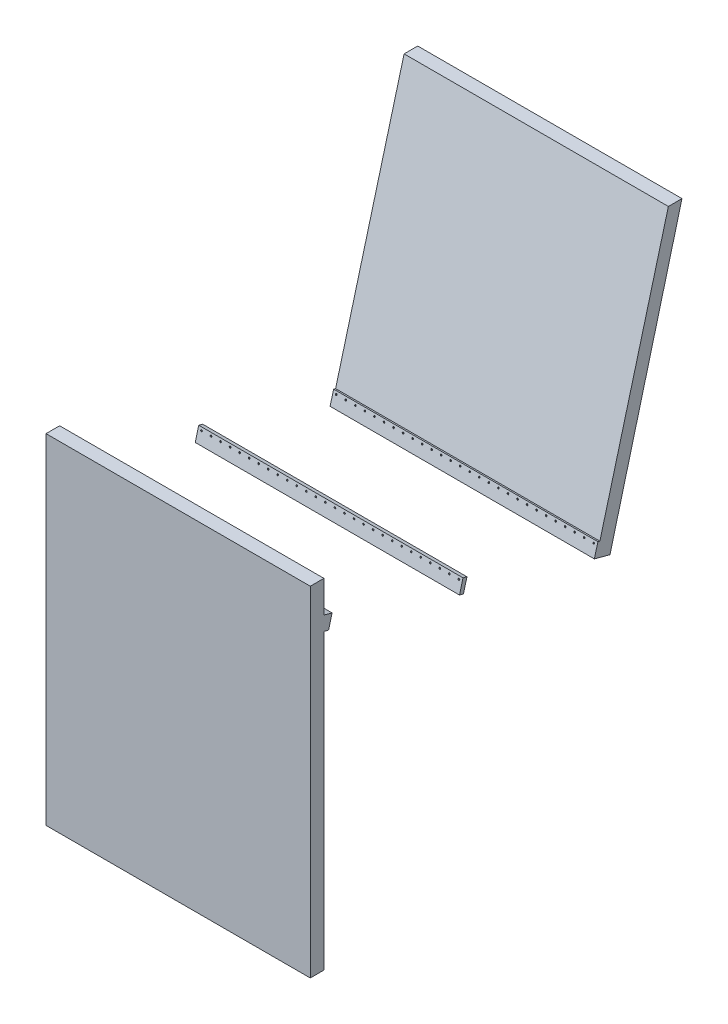
SolidWorks part; units mm, degrees
note: The reader was unsure of these and kept them because the rebuilt part matched: shared geometry of "Sketch1<3>", "Sketch1<5>", "Sketch1<6>".
ref_plane "Front Plane" through (0, 0, 0) normal (0, 0, 1) x (1, 0, 0)
ref_plane "Top Plane" through (0, 0, 0) normal (0, 1, 0) x (1, 0, 0)
ref_plane "Right Plane" through (0, 0, 0) normal (1, 0, 0) x (0, 0, -1)
sketch "Sketch1" plane through (0, 0, 0) normal (0, 1, 0) x (1, 0, 0)
  line L0 (970, -1000) -> (-970, -1000)
  line L1 (-970, -1000) -> (-970, -1100)
  line L2 (-970, -1100) -> (970, -1100)
  line L3 (970, -1100) -> (970, -1000)
  line L4 (-970, 1000) -> (970, 1000)
  line L5 (970, 1000) -> (970, 1100)
  line L6 (970, 1100) -> (-970, 1100)
  line L7 (-970, 1100) -> (-970, 1000)
  point P2 (0, -1000)
  dimension "D1" = 1940
  dimension "D2" = 100
  dimension "D3" = 1000
  dimension "D4" = 100
  dimension "D5" = 1000
  dimension "D6" = 1940
extrude "Boss-Extrude1" add sketch "Sketch1" along normal blind 2000
sketch "Sketch2" plane through (0, 0, 0) normal (1, 0, 0) x (0, 0, -1)
  line L0 (1100, 0) -> (1100, 1200) construction
  line L4 (1100, 2000) -> (1100, 0) construction
  line L7 (1100, 1200) -> (-1100, 1789.4882)
  line L8 (-1100, 2000) -> (-1100, 0) construction
  line L9 (1100, 1200) -> (132.8962, 1200) construction
  line L10 (-1100, 1789.4882) -> (-1100, 2789.4882)
  line L11 (-1100, 2789.4882) -> (1100, 2789.4882)
  line L12 (1100, 2789.4882) -> (1100, 1200)
  dimension "D1" = 1200
  dimension "D2" = 15
  dimension "D3" = 1000
extrude "Cut-Extrude1" cut sketch "Sketch2" against normal through all both and the other way through all
ref_plane "Plane1" through (0, 3200, 0) normal (0, 1, 0) x (1, 0, 0)
sketch "Sketch3" plane through (0, 1394.6152, -373.686) normal (0, 0.9659, -0.2588) x (1, 0, 0)
  line L0 (-970, 648.4079) -> (970, 648.4079)
  line L1 (970, 648.4079) -> (970, 751.9356)
  line L2 (970, 751.9356) -> (-970, 751.9356)
  line L3 (-970, 751.9356) -> (-970, 648.4079)
sketch "Sketch5" plane through (0, 0, 0) normal (1, 0, 0) x (0, 0, -1)
  line L0 (1000, 1226.7949) -> (1000, 2391.2042) construction
  line L1 (1000, 1226.7949) -> (1528.7187, 3200) construction
  line L2 (1067, 3200) -> (-1067, 3200) construction
  dimension "D1" = 15
sketch "Sketch6" plane through (0, 3200, 0) normal (0, 1, 0) x (1, 0, 0)
  line L0 (-970, 1528.7187) -> (970, 1528.7187)
  line L2 (-970, 1100) -> (-970, 1000) construction
  line L4 (0, 1000) -> (0, 1528.7187) construction
  line L5 (-970, 1528.7187) -> (-970, 1628.7187)
  line L6 (-970, 1628.7187) -> (970, 1628.7187)
  line L7 (970, 1628.7187) -> (970, 1528.7187)
  point P3 (0, 1528.7187)
  dimension "D1" = 1940
  dimension "D2" = 100
loft "Loft2" add profiles "Sketch6" section face at (0, 1213.3975, -1050) section "Sketch6"
sketch "Sketch4" plane through (0, 0, 0) normal (1, 0, 0) x (0, 0, -1)
  line L2 (1100, 1200) -> (-1100, 1789.4882)
  line L10 (1100, 1200) -> (1125.5581, 1296.6793)
  line L12 (1125.5581, 1296.6793) -> (-1100, 1893.0158)
  line L13 (-1100, 1893.0158) -> (-1100, 1789.4882)
  line L14 (1100, 1200) -> (1628.7187, 3200) construction
  dimension "D1" = 100
extrude "Boss-Extrude3" add sketch "Sketch4" along normal up to vertex (970 mm away) and the other way up to vertex (970 mm away) up to point (970, 1762.6933, 1000) other way up to point (-970, 1762.6933, 1000)
extrude "Boss-Extrude4" add sketch "Sketch1<3>" along normal blind 2100 contours L0 L1 L2 L3
sketch "Sketch1<3>" plane through (0, 0, 0) normal (0, 1, 0) x (1, 0, 0) same geometry as "Sketch1"
extrude "Cut-Extrude2" cut sketch "Sketch1<5>" along normal up to surface (1226.7949 mm away) contours L6 L7 L4 L5
sketch "Sketch1<5>" plane through (0, 0, 0) normal (0, 1, 0) x (1, 0, 0) same geometry as "Sketch1"
sketch "Sketch7" plane through (0, 1491.2078, -399.5679) normal (0, 0.9659, -0.2588) x (1, 0, 0)
  line L0 (-970, 633.4079) -> (970, 633.4079)
  line L1 (-970, 648.4079) -> (-970, -1448.9393) construction
  line L2 (970, 648.4079) -> (970, -1448.9393) construction
  line L3 (-970, -361.5921) -> (970, -361.5921)
  line L4 (-970, -391.5921) -> (970, -391.5921)
  line L5 (-970, -1386.5921) -> (970, -1386.5921)
  line L6 (-970, 648.4079) -> (970, 648.4079) construction
  line L7 (970, 633.4079) -> (970, -1386.5921)
  line L8 (-970, 633.4079) -> (-970, -1386.5921)
  line M6 (970, -1448.9393) -> (970, 648.4079)
  line M8 (-970, 648.4079) -> (-970, -1448.9393)
  dimension "D1" = 15
  dimension "D2" = 995
  dimension "D3" = 30
  dimension "D4" = 995
extrude "Cut-Extrude3" cut sketch "Sketch7" against normal up to next contours L3 L0 M8 M6 | L5 L4 M8 M6
sketch "Sketch8" plane through (0, -163.938, -611.8251) normal (0, 0.2588, 0.9659) x (1, 0, 0)
  line L0 (-970, 1493.8119) -> (970, 1493.8119) construction
  line L7 (-970, 1443.8119) -> (-970, 1543.8119) construction
  line L8 (970, 1443.8119) -> (970, 1543.8119) construction
  line L11 (0, 1493.8119) -> (0, 1523.8119) construction
  line L167 (-970, 1523.8119) -> (970, 1523.8119) construction
  line L168 (35, 1543.8119) -> (35, 1443.8119) construction
  line L169 (-970, 1543.8119) -> (970, 1543.8119) construction
  line L170 (970, 1443.8119) -> (-970, 1443.8119) construction
  line L171 (-35, 1543.8119) -> (-35, 1443.8119) construction
  line L172 (-108.2079, 1518.2557) -> (-101.7921, 1518.2557)
  line L173 (-28.5842, 1523.8119) -> (-31.7921, 1529.3682)
  line L174 (-31.7921, 1529.3682) -> (-38.2079, 1529.3682)
  line L175 (-38.2079, 1529.3682) -> (-41.4158, 1523.8119)
  line L176 (-41.4158, 1523.8119) -> (-38.2079, 1518.2557)
  line L177 (-38.2079, 1518.2557) -> (-31.7921, 1518.2557)
  line L178 (-31.7921, 1518.2557) -> (-28.5842, 1523.8119)
  line L179 (-101.7921, 1518.2557) -> (-98.5842, 1523.8119)
  line L180 (-98.5842, 1523.8119) -> (-101.7921, 1529.3682)
  line L181 (-101.7921, 1529.3682) -> (-108.2079, 1529.3682)
  line L182 (-108.2079, 1529.3682) -> (-111.4158, 1523.8119)
  line L183 (-111.4158, 1523.8119) -> (-108.2079, 1518.2557)
  line L184 (-178.2079, 1518.2557) -> (-171.7921, 1518.2557)
  line L185 (-171.7921, 1518.2557) -> (-168.5842, 1523.8119)
  line L186 (-168.5842, 1523.8119) -> (-171.7921, 1529.3682)
  line L187 (-171.7921, 1529.3682) -> (-178.2079, 1529.3682)
  line L188 (-178.2079, 1529.3682) -> (-181.4158, 1523.8119)
  line L189 (-181.4158, 1523.8119) -> (-178.2079, 1518.2557)
  line L190 (-248.2079, 1518.2557) -> (-241.7921, 1518.2557)
  line L191 (-241.7921, 1518.2557) -> (-238.5842, 1523.8119)
  line L192 (-238.5842, 1523.8119) -> (-241.7921, 1529.3682)
  line L193 (-241.7921, 1529.3682) -> (-248.2079, 1529.3682)
  line L194 (-248.2079, 1529.3682) -> (-251.4158, 1523.8119)
  line L195 (-251.4158, 1523.8119) -> (-248.2079, 1518.2557)
  line L196 (-318.2079, 1518.2557) -> (-311.7921, 1518.2557)
  line L197 (-311.7921, 1518.2557) -> (-308.5842, 1523.8119)
  line L198 (-308.5842, 1523.8119) -> (-311.7921, 1529.3682)
  line L199 (-311.7921, 1529.3682) -> (-318.2079, 1529.3682)
  line L200 (-318.2079, 1529.3682) -> (-321.4158, 1523.8119)
  line L201 (-321.4158, 1523.8119) -> (-318.2079, 1518.2557)
  line L202 (-388.2079, 1518.2557) -> (-381.7921, 1518.2557)
  line L203 (-381.7921, 1518.2557) -> (-378.5842, 1523.8119)
  line L204 (-378.5842, 1523.8119) -> (-381.7921, 1529.3682)
  line L205 (-381.7921, 1529.3682) -> (-388.2079, 1529.3682)
  line L206 (-388.2079, 1529.3682) -> (-391.4158, 1523.8119)
  line L207 (-391.4158, 1523.8119) -> (-388.2079, 1518.2557)
  line L208 (-458.2079, 1518.2557) -> (-451.7921, 1518.2557)
  line L209 (-451.7921, 1518.2557) -> (-448.5842, 1523.8119)
  line L210 (-448.5842, 1523.8119) -> (-451.7921, 1529.3682)
  line L211 (-451.7921, 1529.3682) -> (-458.2079, 1529.3682)
  line L212 (-458.2079, 1529.3682) -> (-461.4158, 1523.8119)
  line L213 (-461.4158, 1523.8119) -> (-458.2079, 1518.2557)
  line L214 (-528.2079, 1518.2557) -> (-521.7921, 1518.2557)
  line L215 (-521.7921, 1518.2557) -> (-518.5842, 1523.8119)
  line L216 (-518.5842, 1523.8119) -> (-521.7921, 1529.3682)
  line L217 (-521.7921, 1529.3682) -> (-528.2079, 1529.3682)
  line L218 (-528.2079, 1529.3682) -> (-531.4158, 1523.8119)
  line L219 (-531.4158, 1523.8119) -> (-528.2079, 1518.2557)
  line L220 (-598.2079, 1518.2557) -> (-591.7921, 1518.2557)
  line L221 (-591.7921, 1518.2557) -> (-588.5842, 1523.8119)
  line L222 (-588.5842, 1523.8119) -> (-591.7921, 1529.3682)
  line L223 (-591.7921, 1529.3682) -> (-598.2079, 1529.3682)
  line L224 (-598.2079, 1529.3682) -> (-601.4158, 1523.8119)
  line L225 (-601.4158, 1523.8119) -> (-598.2079, 1518.2557)
  line L226 (-668.2079, 1518.2557) -> (-661.7921, 1518.2557)
  line L227 (-661.7921, 1518.2557) -> (-658.5842, 1523.8119)
  line L228 (-658.5842, 1523.8119) -> (-661.7921, 1529.3682)
  line L229 (-661.7921, 1529.3682) -> (-668.2079, 1529.3682)
  line L230 (-668.2079, 1529.3682) -> (-671.4158, 1523.8119)
  line L231 (-671.4158, 1523.8119) -> (-668.2079, 1518.2557)
  line L232 (-738.2079, 1518.2557) -> (-731.7921, 1518.2557)
  line L233 (-731.7921, 1518.2557) -> (-728.5842, 1523.8119)
  line L234 (-728.5842, 1523.8119) -> (-731.7921, 1529.3682)
  line L235 (-731.7921, 1529.3682) -> (-738.2079, 1529.3682)
  line L236 (-738.2079, 1529.3682) -> (-741.4158, 1523.8119)
  line L237 (-741.4158, 1523.8119) -> (-738.2079, 1518.2557)
  line L238 (-808.2079, 1518.2557) -> (-801.7921, 1518.2557)
  line L239 (-801.7921, 1518.2557) -> (-798.5842, 1523.8119)
  line L240 (-798.5842, 1523.8119) -> (-801.7921, 1529.3682)
  line L241 (-801.7921, 1529.3682) -> (-808.2079, 1529.3682)
  line L242 (-808.2079, 1529.3682) -> (-811.4158, 1523.8119)
  line L243 (-811.4158, 1523.8119) -> (-808.2079, 1518.2557)
  line L244 (-878.2079, 1518.2557) -> (-871.7921, 1518.2557)
  line L245 (-871.7921, 1518.2557) -> (-868.5842, 1523.8119)
  line L246 (-868.5842, 1523.8119) -> (-871.7921, 1529.3682)
  line L247 (-871.7921, 1529.3682) -> (-878.2079, 1529.3682)
  line L248 (-878.2079, 1529.3682) -> (-881.4158, 1523.8119)
  line L249 (-881.4158, 1523.8119) -> (-878.2079, 1518.2557)
  line L250 (-948.2079, 1518.2557) -> (-941.7921, 1518.2557)
  line L251 (-941.7921, 1518.2557) -> (-938.5842, 1523.8119)
  line L252 (-938.5842, 1523.8119) -> (-941.7921, 1529.3682)
  line L253 (-941.7921, 1529.3682) -> (-948.2079, 1529.3682)
  line L254 (-948.2079, 1529.3682) -> (-951.4158, 1523.8119)
  line L255 (-951.4158, 1523.8119) -> (-948.2079, 1518.2557)
  line L256 (101.7921, 1518.2557) -> (108.2079, 1518.2557)
  line L257 (41.4158, 1523.8119) -> (38.2079, 1529.3682)
  line L258 (38.2079, 1529.3682) -> (31.7921, 1529.3682)
  line L259 (31.7921, 1529.3682) -> (28.5842, 1523.8119)
  line L260 (28.5842, 1523.8119) -> (31.7921, 1518.2557)
  line L261 (31.7921, 1518.2557) -> (38.2079, 1518.2557)
  line L262 (38.2079, 1518.2557) -> (41.4158, 1523.8119)
  line L263 (108.2079, 1518.2557) -> (111.4158, 1523.8119)
  line L264 (111.4158, 1523.8119) -> (108.2079, 1529.3682)
  line L265 (108.2079, 1529.3682) -> (101.7921, 1529.3682)
  line L266 (101.7921, 1529.3682) -> (98.5842, 1523.8119)
  line L267 (98.5842, 1523.8119) -> (101.7921, 1518.2557)
  line L268 (171.7921, 1518.2557) -> (178.2079, 1518.2557)
  line L269 (178.2079, 1518.2557) -> (181.4158, 1523.8119)
  line L270 (181.4158, 1523.8119) -> (178.2079, 1529.3682)
  line L271 (178.2079, 1529.3682) -> (171.7921, 1529.3682)
  line L272 (171.7921, 1529.3682) -> (168.5842, 1523.8119)
  line L273 (168.5842, 1523.8119) -> (171.7921, 1518.2557)
  line L274 (241.7921, 1518.2557) -> (248.2079, 1518.2557)
  line L275 (248.2079, 1518.2557) -> (251.4158, 1523.8119)
  line L276 (251.4158, 1523.8119) -> (248.2079, 1529.3682)
  line L277 (248.2079, 1529.3682) -> (241.7921, 1529.3682)
  line L278 (241.7921, 1529.3682) -> (238.5842, 1523.8119)
  line L279 (238.5842, 1523.8119) -> (241.7921, 1518.2557)
  line L280 (311.7921, 1518.2557) -> (318.2079, 1518.2557)
  line L281 (318.2079, 1518.2557) -> (321.4158, 1523.8119)
  line L282 (321.4158, 1523.8119) -> (318.2079, 1529.3682)
  line L283 (318.2079, 1529.3682) -> (311.7921, 1529.3682)
  line L284 (311.7921, 1529.3682) -> (308.5842, 1523.8119)
  line L285 (308.5842, 1523.8119) -> (311.7921, 1518.2557)
  line L286 (381.7921, 1518.2557) -> (388.2079, 1518.2557)
  line L287 (388.2079, 1518.2557) -> (391.4158, 1523.8119)
  line L288 (391.4158, 1523.8119) -> (388.2079, 1529.3682)
  line L289 (388.2079, 1529.3682) -> (381.7921, 1529.3682)
  line L290 (381.7921, 1529.3682) -> (378.5842, 1523.8119)
  line L291 (378.5842, 1523.8119) -> (381.7921, 1518.2557)
  line L292 (451.7921, 1518.2557) -> (458.2079, 1518.2557)
  line L293 (458.2079, 1518.2557) -> (461.4158, 1523.8119)
  line L294 (461.4158, 1523.8119) -> (458.2079, 1529.3682)
  line L295 (458.2079, 1529.3682) -> (451.7921, 1529.3682)
  line L296 (451.7921, 1529.3682) -> (448.5842, 1523.8119)
  line L297 (448.5842, 1523.8119) -> (451.7921, 1518.2557)
  line L298 (521.7921, 1518.2557) -> (528.2079, 1518.2557)
  line L299 (528.2079, 1518.2557) -> (531.4158, 1523.8119)
  line L300 (531.4158, 1523.8119) -> (528.2079, 1529.3682)
  line L301 (528.2079, 1529.3682) -> (521.7921, 1529.3682)
  line L302 (521.7921, 1529.3682) -> (518.5842, 1523.8119)
  line L303 (518.5842, 1523.8119) -> (521.7921, 1518.2557)
  line L304 (591.7921, 1518.2557) -> (598.2079, 1518.2557)
  line L305 (598.2079, 1518.2557) -> (601.4158, 1523.8119)
  line L306 (601.4158, 1523.8119) -> (598.2079, 1529.3682)
  line L307 (598.2079, 1529.3682) -> (591.7921, 1529.3682)
  line L308 (591.7921, 1529.3682) -> (588.5842, 1523.8119)
  line L309 (588.5842, 1523.8119) -> (591.7921, 1518.2557)
  line L310 (661.7921, 1518.2557) -> (668.2079, 1518.2557)
  line L311 (668.2079, 1518.2557) -> (671.4158, 1523.8119)
  line L312 (671.4158, 1523.8119) -> (668.2079, 1529.3682)
  line L313 (668.2079, 1529.3682) -> (661.7921, 1529.3682)
  line L314 (661.7921, 1529.3682) -> (658.5842, 1523.8119)
  line L315 (658.5842, 1523.8119) -> (661.7921, 1518.2557)
  line L316 (731.7921, 1518.2557) -> (738.2079, 1518.2557)
  line L317 (738.2079, 1518.2557) -> (741.4158, 1523.8119)
  line L318 (741.4158, 1523.8119) -> (738.2079, 1529.3682)
  line L319 (738.2079, 1529.3682) -> (731.7921, 1529.3682)
  line L320 (731.7921, 1529.3682) -> (728.5842, 1523.8119)
  line L321 (728.5842, 1523.8119) -> (731.7921, 1518.2557)
  line L322 (801.7921, 1518.2557) -> (808.2079, 1518.2557)
  line L323 (808.2079, 1518.2557) -> (811.4158, 1523.8119)
  line L324 (811.4158, 1523.8119) -> (808.2079, 1529.3682)
  line L325 (808.2079, 1529.3682) -> (801.7921, 1529.3682)
  line L326 (801.7921, 1529.3682) -> (798.5842, 1523.8119)
  line L327 (798.5842, 1523.8119) -> (801.7921, 1518.2557)
  line L328 (871.7921, 1518.2557) -> (878.2079, 1518.2557)
  line L329 (878.2079, 1518.2557) -> (881.4158, 1523.8119)
  line L330 (881.4158, 1523.8119) -> (878.2079, 1529.3682)
  line L331 (878.2079, 1529.3682) -> (871.7921, 1529.3682)
  line L332 (871.7921, 1529.3682) -> (868.5842, 1523.8119)
  line L333 (868.5842, 1523.8119) -> (871.7921, 1518.2557)
  line L334 (941.7921, 1518.2557) -> (948.2079, 1518.2557)
  line L335 (948.2079, 1518.2557) -> (951.4158, 1523.8119)
  line L336 (951.4158, 1523.8119) -> (948.2079, 1529.3682)
  line L337 (948.2079, 1529.3682) -> (941.7921, 1529.3682)
  line L338 (941.7921, 1529.3682) -> (938.5842, 1523.8119)
  line L339 (938.5842, 1523.8119) -> (941.7921, 1518.2557)
  circle A0 centre (-35, 1523.8119) radius 5.5562 construction
  circle A1 centre (-105, 1523.8119) radius 5.5562 construction
  circle A2 centre (-175, 1523.8119) radius 5.5562 construction
  circle A3 centre (-245, 1523.8119) radius 5.5562 construction
  circle A4 centre (-315, 1523.8119) radius 5.5562 construction
  circle A5 centre (-385, 1523.8119) radius 5.5562 construction
  circle A6 centre (-455, 1523.8119) radius 5.5562 construction
  circle A7 centre (-525, 1523.8119) radius 5.5562 construction
  circle A8 centre (-595, 1523.8119) radius 5.5562 construction
  circle A9 centre (-665, 1523.8119) radius 5.5562 construction
  circle A10 centre (-735, 1523.8119) radius 5.5562 construction
  circle A11 centre (-805, 1523.8119) radius 5.5562 construction
  circle A12 centre (-875, 1523.8119) radius 5.5562 construction
  circle A13 centre (-945, 1523.8119) radius 5.5562 construction
  circle A14 centre (35, 1523.8119) radius 5.5562 construction
  circle A15 centre (105, 1523.8119) radius 5.5562 construction
  circle A16 centre (175, 1523.8119) radius 5.5562 construction
  circle A17 centre (245, 1523.8119) radius 5.5562 construction
  circle A18 centre (315, 1523.8119) radius 5.5562 construction
  circle A19 centre (385, 1523.8119) radius 5.5562 construction
  circle A20 centre (455, 1523.8119) radius 5.5562 construction
  circle A21 centre (525, 1523.8119) radius 5.5562 construction
  circle A22 centre (595, 1523.8119) radius 5.5562 construction
  circle A23 centre (665, 1523.8119) radius 5.5562 construction
  circle A24 centre (735, 1523.8119) radius 5.5562 construction
  circle A25 centre (805, 1523.8119) radius 5.5562 construction
  circle A26 centre (875, 1523.8119) radius 5.5562 construction
  circle A27 centre (945, 1523.8119) radius 5.5562 construction
  point P13 (0, 1523.8119)
  dimension "D1" = 30
  dimension "D2" = 35
  dimension "D5" = 14
  dimension "D6" = 11.1125
  dimension "D3" = 35
  dimension "D4" = 11.1125
sketch "Sketch9" plane through (0, 93.5869, 349.2711) normal (0, -0.2588, -0.9659) x (-1, 0, 0)
  line L0 (-970, 1493.8119) -> (970, 1493.8119) construction
  line L1 (-970, 1443.8119) -> (-970, 1543.8119) construction
  line L2 (970, 1443.8119) -> (970, 1543.8119) construction
  line L10 (0, 1493.8119) -> (0, 1523.8119) construction
  line L168 (-970, 1523.8119) -> (970, 1523.8119) construction
  line L169 (-35, 1543.8119) -> (-35, 1443.8119) construction
  line L170 (970, 1543.8119) -> (-970, 1543.8119) construction
  line L171 (-970, 1443.8119) -> (970, 1443.8119) construction
  line L172 (35, 1543.8119) -> (35, 1443.8119) construction
  line L173 (108.2079, 1529.3682) -> (101.7921, 1529.3682)
  line L174 (-28.5842, 1523.8119) -> (-31.7921, 1529.3682)
  line L175 (-31.7921, 1529.3682) -> (-38.2079, 1529.3682)
  line L176 (-38.2079, 1529.3682) -> (-41.4158, 1523.8119)
  line L177 (-41.4158, 1523.8119) -> (-38.2079, 1518.2557)
  line L178 (-38.2079, 1518.2557) -> (-31.7921, 1518.2557)
  line L179 (-31.7921, 1518.2557) -> (-28.5842, 1523.8119)
  line L180 (41.4158, 1523.8119) -> (38.2079, 1529.3682)
  line L181 (38.2079, 1529.3682) -> (31.7921, 1529.3682)
  line L182 (31.7921, 1529.3682) -> (28.5842, 1523.8119)
  line L183 (28.5842, 1523.8119) -> (31.7921, 1518.2557)
  line L184 (31.7921, 1518.2557) -> (38.2079, 1518.2557)
  line L185 (38.2079, 1518.2557) -> (41.4158, 1523.8119)
  line L186 (111.4158, 1523.8119) -> (108.2079, 1529.3682)
  line L187 (101.7921, 1529.3682) -> (98.5842, 1523.8119)
  line L188 (98.5842, 1523.8119) -> (101.7921, 1518.2557)
  line L189 (101.7921, 1518.2557) -> (108.2079, 1518.2557)
  line L190 (108.2079, 1518.2557) -> (111.4158, 1523.8119)
  line L191 (178.2079, 1529.3682) -> (171.7921, 1529.3682)
  line L192 (181.4158, 1523.8119) -> (178.2079, 1529.3682)
  line L193 (171.7921, 1529.3682) -> (168.5842, 1523.8119)
  line L194 (168.5842, 1523.8119) -> (171.7921, 1518.2557)
  line L195 (171.7921, 1518.2557) -> (178.2079, 1518.2557)
  line L196 (178.2079, 1518.2557) -> (181.4158, 1523.8119)
  line L197 (248.2079, 1529.3682) -> (241.7921, 1529.3682)
  line L198 (251.4158, 1523.8119) -> (248.2079, 1529.3682)
  line L199 (241.7921, 1529.3682) -> (238.5842, 1523.8119)
  line L200 (238.5842, 1523.8119) -> (241.7921, 1518.2557)
  line L201 (241.7921, 1518.2557) -> (248.2079, 1518.2557)
  line L202 (248.2079, 1518.2557) -> (251.4158, 1523.8119)
  line L203 (318.2079, 1529.3682) -> (311.7921, 1529.3682)
  line L204 (321.4158, 1523.8119) -> (318.2079, 1529.3682)
  line L205 (311.7921, 1529.3682) -> (308.5842, 1523.8119)
  line L206 (308.5842, 1523.8119) -> (311.7921, 1518.2557)
  line L207 (311.7921, 1518.2557) -> (318.2079, 1518.2557)
  line L208 (318.2079, 1518.2557) -> (321.4158, 1523.8119)
  line L209 (388.2079, 1529.3682) -> (381.7921, 1529.3682)
  line L210 (391.4158, 1523.8119) -> (388.2079, 1529.3682)
  line L211 (381.7921, 1529.3682) -> (378.5842, 1523.8119)
  line L212 (378.5842, 1523.8119) -> (381.7921, 1518.2557)
  line L213 (381.7921, 1518.2557) -> (388.2079, 1518.2557)
  line L214 (388.2079, 1518.2557) -> (391.4158, 1523.8119)
  line L215 (458.2079, 1529.3682) -> (451.7921, 1529.3682)
  line L216 (461.4158, 1523.8119) -> (458.2079, 1529.3682)
  line L217 (451.7921, 1529.3682) -> (448.5842, 1523.8119)
  line L218 (448.5842, 1523.8119) -> (451.7921, 1518.2557)
  line L219 (451.7921, 1518.2557) -> (458.2079, 1518.2557)
  line L220 (458.2079, 1518.2557) -> (461.4158, 1523.8119)
  line L221 (528.2079, 1529.3682) -> (521.7921, 1529.3682)
  line L222 (531.4158, 1523.8119) -> (528.2079, 1529.3682)
  line L223 (521.7921, 1529.3682) -> (518.5842, 1523.8119)
  line L224 (518.5842, 1523.8119) -> (521.7921, 1518.2557)
  line L225 (521.7921, 1518.2557) -> (528.2079, 1518.2557)
  line L226 (528.2079, 1518.2557) -> (531.4158, 1523.8119)
  line L227 (598.2079, 1529.3682) -> (591.7921, 1529.3682)
  line L228 (601.4158, 1523.8119) -> (598.2079, 1529.3682)
  line L229 (591.7921, 1529.3682) -> (588.5842, 1523.8119)
  line L230 (588.5842, 1523.8119) -> (591.7921, 1518.2557)
  line L231 (591.7921, 1518.2557) -> (598.2079, 1518.2557)
  line L232 (598.2079, 1518.2557) -> (601.4158, 1523.8119)
  line L233 (668.2079, 1529.3682) -> (661.7921, 1529.3682)
  line L234 (671.4158, 1523.8119) -> (668.2079, 1529.3682)
  line L235 (661.7921, 1529.3682) -> (658.5842, 1523.8119)
  line L236 (658.5842, 1523.8119) -> (661.7921, 1518.2557)
  line L237 (661.7921, 1518.2557) -> (668.2079, 1518.2557)
  line L238 (668.2079, 1518.2557) -> (671.4158, 1523.8119)
  line L239 (738.2079, 1529.3682) -> (731.7921, 1529.3682)
  line L240 (741.4158, 1523.8119) -> (738.2079, 1529.3682)
  line L241 (731.7921, 1529.3682) -> (728.5842, 1523.8119)
  line L242 (728.5842, 1523.8119) -> (731.7921, 1518.2557)
  line L243 (731.7921, 1518.2557) -> (738.2079, 1518.2557)
  line L244 (738.2079, 1518.2557) -> (741.4158, 1523.8119)
  line L245 (808.2079, 1529.3682) -> (801.7921, 1529.3682)
  line L246 (811.4158, 1523.8119) -> (808.2079, 1529.3682)
  line L247 (801.7921, 1529.3682) -> (798.5842, 1523.8119)
  line L248 (798.5842, 1523.8119) -> (801.7921, 1518.2557)
  line L249 (801.7921, 1518.2557) -> (808.2079, 1518.2557)
  line L250 (808.2079, 1518.2557) -> (811.4158, 1523.8119)
  line L251 (878.2079, 1529.3682) -> (871.7921, 1529.3682)
  line L252 (881.4158, 1523.8119) -> (878.2079, 1529.3682)
  line L253 (871.7921, 1529.3682) -> (868.5842, 1523.8119)
  line L254 (868.5842, 1523.8119) -> (871.7921, 1518.2557)
  line L255 (871.7921, 1518.2557) -> (878.2079, 1518.2557)
  line L256 (878.2079, 1518.2557) -> (881.4158, 1523.8119)
  line L257 (948.2079, 1529.3682) -> (941.7921, 1529.3682)
  line L258 (951.4158, 1523.8119) -> (948.2079, 1529.3682)
  line L259 (941.7921, 1529.3682) -> (938.5842, 1523.8119)
  line L260 (938.5842, 1523.8119) -> (941.7921, 1518.2557)
  line L261 (941.7921, 1518.2557) -> (948.2079, 1518.2557)
  line L262 (948.2079, 1518.2557) -> (951.4158, 1523.8119)
  line L263 (-101.7921, 1529.3682) -> (-108.2079, 1529.3682)
  line L264 (-108.2079, 1529.3682) -> (-111.4158, 1523.8119)
  line L265 (-111.4158, 1523.8119) -> (-108.2079, 1518.2557)
  line L266 (-108.2079, 1518.2557) -> (-101.7921, 1518.2557)
  line L267 (-101.7921, 1518.2557) -> (-98.5842, 1523.8119)
  line L268 (-98.5842, 1523.8119) -> (-101.7921, 1529.3682)
  line L269 (-171.7921, 1529.3682) -> (-178.2079, 1529.3682)
  line L270 (-178.2079, 1529.3682) -> (-181.4158, 1523.8119)
  line L271 (-181.4158, 1523.8119) -> (-178.2079, 1518.2557)
  line L272 (-178.2079, 1518.2557) -> (-171.7921, 1518.2557)
  line L273 (-171.7921, 1518.2557) -> (-168.5842, 1523.8119)
  line L274 (-168.5842, 1523.8119) -> (-171.7921, 1529.3682)
  line L275 (-241.7921, 1529.3682) -> (-248.2079, 1529.3682)
  line L276 (-248.2079, 1529.3682) -> (-251.4158, 1523.8119)
  line L277 (-251.4158, 1523.8119) -> (-248.2079, 1518.2557)
  line L278 (-248.2079, 1518.2557) -> (-241.7921, 1518.2557)
  line L279 (-241.7921, 1518.2557) -> (-238.5842, 1523.8119)
  line L280 (-238.5842, 1523.8119) -> (-241.7921, 1529.3682)
  line L281 (-311.7921, 1529.3682) -> (-318.2079, 1529.3682)
  line L282 (-318.2079, 1529.3682) -> (-321.4158, 1523.8119)
  line L283 (-321.4158, 1523.8119) -> (-318.2079, 1518.2557)
  line L284 (-318.2079, 1518.2557) -> (-311.7921, 1518.2557)
  line L285 (-311.7921, 1518.2557) -> (-308.5842, 1523.8119)
  line L286 (-308.5842, 1523.8119) -> (-311.7921, 1529.3682)
  line L287 (-381.7921, 1529.3682) -> (-388.2079, 1529.3682)
  line L288 (-388.2079, 1529.3682) -> (-391.4158, 1523.8119)
  line L289 (-391.4158, 1523.8119) -> (-388.2079, 1518.2557)
  line L290 (-388.2079, 1518.2557) -> (-381.7921, 1518.2557)
  line L291 (-381.7921, 1518.2557) -> (-378.5842, 1523.8119)
  line L292 (-378.5842, 1523.8119) -> (-381.7921, 1529.3682)
  line L293 (-451.7921, 1529.3682) -> (-458.2079, 1529.3682)
  line L294 (-458.2079, 1529.3682) -> (-461.4158, 1523.8119)
  line L295 (-461.4158, 1523.8119) -> (-458.2079, 1518.2557)
  line L296 (-458.2079, 1518.2557) -> (-451.7921, 1518.2557)
  line L297 (-451.7921, 1518.2557) -> (-448.5842, 1523.8119)
  line L298 (-448.5842, 1523.8119) -> (-451.7921, 1529.3682)
  line L299 (-521.7921, 1529.3682) -> (-528.2079, 1529.3682)
  line L300 (-528.2079, 1529.3682) -> (-531.4158, 1523.8119)
  line L301 (-531.4158, 1523.8119) -> (-528.2079, 1518.2557)
  line L302 (-528.2079, 1518.2557) -> (-521.7921, 1518.2557)
  line L303 (-521.7921, 1518.2557) -> (-518.5842, 1523.8119)
  line L304 (-518.5842, 1523.8119) -> (-521.7921, 1529.3682)
  line L305 (-591.7921, 1529.3682) -> (-598.2079, 1529.3682)
  line L306 (-598.2079, 1529.3682) -> (-601.4158, 1523.8119)
  line L307 (-601.4158, 1523.8119) -> (-598.2079, 1518.2557)
  line L308 (-598.2079, 1518.2557) -> (-591.7921, 1518.2557)
  line L309 (-591.7921, 1518.2557) -> (-588.5842, 1523.8119)
  line L310 (-588.5842, 1523.8119) -> (-591.7921, 1529.3682)
  line L311 (-661.7921, 1529.3682) -> (-668.2079, 1529.3682)
  line L312 (-668.2079, 1529.3682) -> (-671.4158, 1523.8119)
  line L313 (-671.4158, 1523.8119) -> (-668.2079, 1518.2557)
  line L314 (-668.2079, 1518.2557) -> (-661.7921, 1518.2557)
  line L315 (-661.7921, 1518.2557) -> (-658.5842, 1523.8119)
  line L316 (-658.5842, 1523.8119) -> (-661.7921, 1529.3682)
  line L317 (-731.7921, 1529.3682) -> (-738.2079, 1529.3682)
  line L318 (-738.2079, 1529.3682) -> (-741.4158, 1523.8119)
  line L319 (-741.4158, 1523.8119) -> (-738.2079, 1518.2557)
  line L320 (-738.2079, 1518.2557) -> (-731.7921, 1518.2557)
  line L321 (-731.7921, 1518.2557) -> (-728.5842, 1523.8119)
  line L322 (-728.5842, 1523.8119) -> (-731.7921, 1529.3682)
  line L323 (-801.7921, 1529.3682) -> (-808.2079, 1529.3682)
  line L324 (-808.2079, 1529.3682) -> (-811.4158, 1523.8119)
  line L325 (-811.4158, 1523.8119) -> (-808.2079, 1518.2557)
  line L326 (-808.2079, 1518.2557) -> (-801.7921, 1518.2557)
  line L327 (-801.7921, 1518.2557) -> (-798.5842, 1523.8119)
  line L328 (-798.5842, 1523.8119) -> (-801.7921, 1529.3682)
  line L329 (-871.7921, 1529.3682) -> (-878.2079, 1529.3682)
  line L330 (-878.2079, 1529.3682) -> (-881.4158, 1523.8119)
  line L331 (-881.4158, 1523.8119) -> (-878.2079, 1518.2557)
  line L332 (-878.2079, 1518.2557) -> (-871.7921, 1518.2557)
  line L333 (-871.7921, 1518.2557) -> (-868.5842, 1523.8119)
  line L334 (-868.5842, 1523.8119) -> (-871.7921, 1529.3682)
  line L335 (-941.7921, 1529.3682) -> (-948.2079, 1529.3682)
  line L336 (-948.2079, 1529.3682) -> (-951.4158, 1523.8119)
  line L337 (-951.4158, 1523.8119) -> (-948.2079, 1518.2557)
  line L338 (-948.2079, 1518.2557) -> (-941.7921, 1518.2557)
  line L339 (-941.7921, 1518.2557) -> (-938.5842, 1523.8119)
  line L340 (-938.5842, 1523.8119) -> (-941.7921, 1529.3682)
  circle A0 centre (-35, 1523.8119) radius 5.5563 construction
  circle A1 centre (35, 1523.8119) radius 5.5563 construction
  circle A2 centre (105, 1523.8119) radius 5.5563 construction
  circle A3 centre (175, 1523.8119) radius 5.5563 construction
  circle A4 centre (245, 1523.8119) radius 5.5563 construction
  circle A5 centre (315, 1523.8119) radius 5.5563 construction
  circle A6 centre (385, 1523.8119) radius 5.5563 construction
  circle A7 centre (455, 1523.8119) radius 5.5563 construction
  circle A8 centre (525, 1523.8119) radius 5.5563 construction
  circle A9 centre (595, 1523.8119) radius 5.5563 construction
  circle A10 centre (665, 1523.8119) radius 5.5563 construction
  circle A11 centre (735, 1523.8119) radius 5.5563 construction
  circle A12 centre (805, 1523.8119) radius 5.5563 construction
  circle A13 centre (875, 1523.8119) radius 5.5563 construction
  circle A14 centre (945, 1523.8119) radius 5.5563 construction
  circle A15 centre (-105, 1523.8119) radius 5.5563 construction
  circle A16 centre (-175, 1523.8119) radius 5.5563 construction
  circle A17 centre (-245, 1523.8119) radius 5.5563 construction
  circle A18 centre (-315, 1523.8119) radius 5.5563 construction
  circle A19 centre (-385, 1523.8119) radius 5.5563 construction
  circle A20 centre (-455, 1523.8119) radius 5.5563 construction
  circle A21 centre (-525, 1523.8119) radius 5.5563 construction
  circle A22 centre (-595, 1523.8119) radius 5.5563 construction
  circle A23 centre (-665, 1523.8119) radius 5.5563 construction
  circle A24 centre (-735, 1523.8119) radius 5.5563 construction
  circle A25 centre (-805, 1523.8119) radius 5.5563 construction
  circle A26 centre (-875, 1523.8119) radius 5.5563 construction
  circle A27 centre (-945, 1523.8119) radius 5.5563 construction
  point P15 (0, 1523.8119)
  dimension "D1" = 30
  dimension "D2" = 35
  dimension "D5" = 11.1125
  dimension "D3" = 35
  dimension "D4" = 11.1125
extrude "Cut-Extrude4" cut sketch "Sketch8" against normal blind 15
extrude "Cut-Extrude5" cut sketch "Sketch9" against normal blind 30
sketch "Sketch10" plane through (0, 358.8764, 1339.3451) normal (0, -0.2588, -0.9659) x (-1, 0, 0)
  line L0 (970, 1493.8119) -> (-970, 1493.8119) construction
  line L1 (970, 1443.8119) -> (970, 1543.8119) construction
  line L2 (-970, 1443.8119) -> (-970, 1543.8119) construction
  line L11 (0, 1493.8119) -> (0, 1523.8119) construction
  line L167 (-970, 1523.8119) -> (970, 1523.8119) construction
  line L168 (-35, 1543.8119) -> (-35, 1443.8119) construction
  line L169 (970, 1543.8119) -> (-970, 1543.8119) construction
  line L170 (-970, 1443.8119) -> (970, 1443.8119) construction
  line L173 (35, 1543.8119) -> (35, 1443.8119) construction
  line L174 (108.2079, 1518.2557) -> (111.4158, 1523.8119)
  line L175 (-28.5842, 1523.8119) -> (-31.7921, 1529.3682)
  line L176 (-31.7921, 1529.3682) -> (-38.2079, 1529.3682)
  line L177 (-38.2079, 1529.3682) -> (-41.4158, 1523.8119)
  line L178 (-41.4158, 1523.8119) -> (-38.2079, 1518.2557)
  line L179 (-38.2079, 1518.2557) -> (-31.7921, 1518.2557)
  line L180 (-31.7921, 1518.2557) -> (-28.5842, 1523.8119)
  line L181 (41.4158, 1523.8119) -> (38.2079, 1529.3682)
  line L182 (38.2079, 1529.3682) -> (31.7921, 1529.3682)
  line L183 (31.7921, 1529.3682) -> (28.5842, 1523.8119)
  line L184 (28.5842, 1523.8119) -> (31.7921, 1518.2557)
  line L185 (31.7921, 1518.2557) -> (38.2079, 1518.2557)
  line L186 (38.2079, 1518.2557) -> (41.4158, 1523.8119)
  line L187 (101.7921, 1518.2557) -> (108.2079, 1518.2557)
  line L188 (98.5842, 1523.8119) -> (101.7921, 1518.2557)
  line L189 (101.7921, 1529.3682) -> (98.5842, 1523.8119)
  line L190 (108.2079, 1529.3682) -> (101.7921, 1529.3682)
  line L191 (111.4158, 1523.8119) -> (108.2079, 1529.3682)
  line L192 (178.2079, 1518.2557) -> (181.4158, 1523.8119)
  line L193 (171.7921, 1518.2557) -> (178.2079, 1518.2557)
  line L194 (168.5842, 1523.8119) -> (171.7921, 1518.2557)
  line L195 (171.7921, 1529.3682) -> (168.5842, 1523.8119)
  line L196 (178.2079, 1529.3682) -> (171.7921, 1529.3682)
  line L197 (181.4158, 1523.8119) -> (178.2079, 1529.3682)
  line L198 (248.2079, 1518.2557) -> (251.4158, 1523.8119)
  line L199 (241.7921, 1518.2557) -> (248.2079, 1518.2557)
  line L200 (238.5842, 1523.8119) -> (241.7921, 1518.2557)
  line L201 (241.7921, 1529.3682) -> (238.5842, 1523.8119)
  line L202 (248.2079, 1529.3682) -> (241.7921, 1529.3682)
  line L203 (251.4158, 1523.8119) -> (248.2079, 1529.3682)
  line L204 (318.2079, 1518.2557) -> (321.4158, 1523.8119)
  line L205 (311.7921, 1518.2557) -> (318.2079, 1518.2557)
  line L206 (308.5842, 1523.8119) -> (311.7921, 1518.2557)
  line L207 (311.7921, 1529.3682) -> (308.5842, 1523.8119)
  line L208 (318.2079, 1529.3682) -> (311.7921, 1529.3682)
  line L209 (321.4158, 1523.8119) -> (318.2079, 1529.3682)
  line L210 (388.2079, 1518.2557) -> (391.4158, 1523.8119)
  line L211 (381.7921, 1518.2557) -> (388.2079, 1518.2557)
  line L212 (378.5842, 1523.8119) -> (381.7921, 1518.2557)
  line L213 (381.7921, 1529.3682) -> (378.5842, 1523.8119)
  line L214 (388.2079, 1529.3682) -> (381.7921, 1529.3682)
  line L215 (391.4158, 1523.8119) -> (388.2079, 1529.3682)
  line L216 (458.2079, 1518.2557) -> (461.4158, 1523.8119)
  line L217 (451.7921, 1518.2557) -> (458.2079, 1518.2557)
  line L218 (448.5842, 1523.8119) -> (451.7921, 1518.2557)
  line L219 (451.7921, 1529.3682) -> (448.5842, 1523.8119)
  line L220 (458.2079, 1529.3682) -> (451.7921, 1529.3682)
  line L221 (461.4158, 1523.8119) -> (458.2079, 1529.3682)
  line L222 (528.2079, 1518.2557) -> (531.4158, 1523.8119)
  line L223 (521.7921, 1518.2557) -> (528.2079, 1518.2557)
  line L224 (518.5842, 1523.8119) -> (521.7921, 1518.2557)
  line L225 (521.7921, 1529.3682) -> (518.5842, 1523.8119)
  line L226 (528.2079, 1529.3682) -> (521.7921, 1529.3682)
  line L227 (531.4158, 1523.8119) -> (528.2079, 1529.3682)
  line L228 (598.2079, 1518.2557) -> (601.4158, 1523.8119)
  line L229 (591.7921, 1518.2557) -> (598.2079, 1518.2557)
  line L230 (588.5842, 1523.8119) -> (591.7921, 1518.2557)
  line L231 (591.7921, 1529.3682) -> (588.5842, 1523.8119)
  line L232 (598.2079, 1529.3682) -> (591.7921, 1529.3682)
  line L233 (601.4158, 1523.8119) -> (598.2079, 1529.3682)
  line L234 (668.2079, 1518.2557) -> (671.4158, 1523.8119)
  line L235 (661.7921, 1518.2557) -> (668.2079, 1518.2557)
  line L236 (658.5842, 1523.8119) -> (661.7921, 1518.2557)
  line L237 (661.7921, 1529.3682) -> (658.5842, 1523.8119)
  line L238 (668.2079, 1529.3682) -> (661.7921, 1529.3682)
  line L239 (671.4158, 1523.8119) -> (668.2079, 1529.3682)
  line L240 (738.2079, 1518.2557) -> (741.4158, 1523.8119)
  line L241 (731.7921, 1518.2557) -> (738.2079, 1518.2557)
  line L242 (728.5842, 1523.8119) -> (731.7921, 1518.2557)
  line L243 (731.7921, 1529.3682) -> (728.5842, 1523.8119)
  line L244 (738.2079, 1529.3682) -> (731.7921, 1529.3682)
  line L245 (741.4158, 1523.8119) -> (738.2079, 1529.3682)
  line L246 (808.2079, 1518.2557) -> (811.4158, 1523.8119)
  line L247 (801.7921, 1518.2557) -> (808.2079, 1518.2557)
  line L248 (798.5842, 1523.8119) -> (801.7921, 1518.2557)
  line L249 (801.7921, 1529.3682) -> (798.5842, 1523.8119)
  line L250 (808.2079, 1529.3682) -> (801.7921, 1529.3682)
  line L251 (811.4158, 1523.8119) -> (808.2079, 1529.3682)
  line L252 (878.2079, 1518.2557) -> (881.4158, 1523.8119)
  line L253 (871.7921, 1518.2557) -> (878.2079, 1518.2557)
  line L254 (868.5842, 1523.8119) -> (871.7921, 1518.2557)
  line L255 (871.7921, 1529.3682) -> (868.5842, 1523.8119)
  line L256 (878.2079, 1529.3682) -> (871.7921, 1529.3682)
  line L257 (881.4158, 1523.8119) -> (878.2079, 1529.3682)
  line L258 (948.2079, 1518.2557) -> (951.4158, 1523.8119)
  line L259 (941.7921, 1518.2557) -> (948.2079, 1518.2557)
  line L260 (938.5842, 1523.8119) -> (941.7921, 1518.2557)
  line L261 (941.7921, 1529.3682) -> (938.5842, 1523.8119)
  line L262 (948.2079, 1529.3682) -> (941.7921, 1529.3682)
  line L263 (951.4158, 1523.8119) -> (948.2079, 1529.3682)
  line L264 (-101.7921, 1529.3682) -> (-108.2079, 1529.3682)
  line L265 (-108.2079, 1529.3682) -> (-111.4158, 1523.8119)
  line L266 (-111.4158, 1523.8119) -> (-108.2079, 1518.2557)
  line L267 (-108.2079, 1518.2557) -> (-101.7921, 1518.2557)
  line L268 (-101.7921, 1518.2557) -> (-98.5842, 1523.8119)
  line L269 (-98.5842, 1523.8119) -> (-101.7921, 1529.3682)
  line L270 (-171.7921, 1529.3682) -> (-178.2079, 1529.3682)
  line L271 (-178.2079, 1529.3682) -> (-181.4158, 1523.8119)
  line L272 (-181.4158, 1523.8119) -> (-178.2079, 1518.2557)
  line L273 (-178.2079, 1518.2557) -> (-171.7921, 1518.2557)
  line L274 (-171.7921, 1518.2557) -> (-168.5842, 1523.8119)
  line L275 (-168.5842, 1523.8119) -> (-171.7921, 1529.3682)
  line L276 (-241.7921, 1529.3682) -> (-248.2079, 1529.3682)
  line L277 (-248.2079, 1529.3682) -> (-251.4158, 1523.8119)
  line L278 (-251.4158, 1523.8119) -> (-248.2079, 1518.2557)
  line L279 (-248.2079, 1518.2557) -> (-241.7921, 1518.2557)
  line L280 (-241.7921, 1518.2557) -> (-238.5842, 1523.8119)
  line L281 (-238.5842, 1523.8119) -> (-241.7921, 1529.3682)
  line L282 (-311.7921, 1529.3682) -> (-318.2079, 1529.3682)
  line L283 (-318.2079, 1529.3682) -> (-321.4158, 1523.8119)
  line L284 (-321.4158, 1523.8119) -> (-318.2079, 1518.2557)
  line L285 (-318.2079, 1518.2557) -> (-311.7921, 1518.2557)
  line L286 (-311.7921, 1518.2557) -> (-308.5842, 1523.8119)
  line L287 (-308.5842, 1523.8119) -> (-311.7921, 1529.3682)
  line L288 (-381.7921, 1529.3682) -> (-388.2079, 1529.3682)
  line L289 (-388.2079, 1529.3682) -> (-391.4158, 1523.8119)
  line L290 (-391.4158, 1523.8119) -> (-388.2079, 1518.2557)
  line L291 (-388.2079, 1518.2557) -> (-381.7921, 1518.2557)
  line L292 (-381.7921, 1518.2557) -> (-378.5842, 1523.8119)
  line L293 (-378.5842, 1523.8119) -> (-381.7921, 1529.3682)
  line L294 (-451.7921, 1529.3682) -> (-458.2079, 1529.3682)
  line L295 (-458.2079, 1529.3682) -> (-461.4158, 1523.8119)
  line L296 (-461.4158, 1523.8119) -> (-458.2079, 1518.2557)
  line L297 (-458.2079, 1518.2557) -> (-451.7921, 1518.2557)
  line L298 (-451.7921, 1518.2557) -> (-448.5842, 1523.8119)
  line L299 (-448.5842, 1523.8119) -> (-451.7921, 1529.3682)
  line L300 (-521.7921, 1529.3682) -> (-528.2079, 1529.3682)
  line L301 (-528.2079, 1529.3682) -> (-531.4158, 1523.8119)
  line L302 (-531.4158, 1523.8119) -> (-528.2079, 1518.2557)
  line L303 (-528.2079, 1518.2557) -> (-521.7921, 1518.2557)
  line L304 (-521.7921, 1518.2557) -> (-518.5842, 1523.8119)
  line L305 (-518.5842, 1523.8119) -> (-521.7921, 1529.3682)
  line L306 (-591.7921, 1529.3682) -> (-598.2079, 1529.3682)
  line L307 (-598.2079, 1529.3682) -> (-601.4158, 1523.8119)
  line L308 (-601.4158, 1523.8119) -> (-598.2079, 1518.2557)
  line L309 (-598.2079, 1518.2557) -> (-591.7921, 1518.2557)
  line L310 (-591.7921, 1518.2557) -> (-588.5842, 1523.8119)
  line L311 (-588.5842, 1523.8119) -> (-591.7921, 1529.3682)
  line L312 (-661.7921, 1529.3682) -> (-668.2079, 1529.3682)
  line L313 (-668.2079, 1529.3682) -> (-671.4158, 1523.8119)
  line L314 (-671.4158, 1523.8119) -> (-668.2079, 1518.2557)
  line L315 (-668.2079, 1518.2557) -> (-661.7921, 1518.2557)
  line L316 (-661.7921, 1518.2557) -> (-658.5842, 1523.8119)
  line L317 (-658.5842, 1523.8119) -> (-661.7921, 1529.3682)
  line L318 (-731.7921, 1529.3682) -> (-738.2079, 1529.3682)
  line L319 (-738.2079, 1529.3682) -> (-741.4158, 1523.8119)
  line L320 (-741.4158, 1523.8119) -> (-738.2079, 1518.2557)
  line L321 (-738.2079, 1518.2557) -> (-731.7921, 1518.2557)
  line L322 (-731.7921, 1518.2557) -> (-728.5842, 1523.8119)
  line L323 (-728.5842, 1523.8119) -> (-731.7921, 1529.3682)
  line L324 (-801.7921, 1529.3682) -> (-808.2079, 1529.3682)
  line L325 (-808.2079, 1529.3682) -> (-811.4158, 1523.8119)
  line L326 (-811.4158, 1523.8119) -> (-808.2079, 1518.2557)
  line L327 (-808.2079, 1518.2557) -> (-801.7921, 1518.2557)
  line L328 (-801.7921, 1518.2557) -> (-798.5842, 1523.8119)
  line L329 (-798.5842, 1523.8119) -> (-801.7921, 1529.3682)
  line L330 (-871.7921, 1529.3682) -> (-878.2079, 1529.3682)
  line L331 (-878.2079, 1529.3682) -> (-881.4158, 1523.8119)
  line L332 (-881.4158, 1523.8119) -> (-878.2079, 1518.2557)
  line L333 (-878.2079, 1518.2557) -> (-871.7921, 1518.2557)
  line L334 (-871.7921, 1518.2557) -> (-868.5842, 1523.8119)
  line L335 (-868.5842, 1523.8119) -> (-871.7921, 1529.3682)
  line L336 (-941.7921, 1529.3682) -> (-948.2079, 1529.3682)
  line L337 (-948.2079, 1529.3682) -> (-951.4158, 1523.8119)
  line L338 (-951.4158, 1523.8119) -> (-948.2079, 1518.2557)
  line L339 (-948.2079, 1518.2557) -> (-941.7921, 1518.2557)
  line L340 (-941.7921, 1518.2557) -> (-938.5842, 1523.8119)
  line L341 (-938.5842, 1523.8119) -> (-941.7921, 1529.3682)
  circle A0 centre (-35, 1523.8119) radius 5.5563 construction
  circle A1 centre (35, 1523.8119) radius 5.5563 construction
  circle A2 centre (105, 1523.8119) radius 5.5563 construction
  circle A3 centre (175, 1523.8119) radius 5.5563 construction
  circle A4 centre (245, 1523.8119) radius 5.5563 construction
  circle A5 centre (315, 1523.8119) radius 5.5563 construction
  circle A6 centre (385, 1523.8119) radius 5.5563 construction
  circle A7 centre (455, 1523.8119) radius 5.5563 construction
  circle A8 centre (525, 1523.8119) radius 5.5563 construction
  circle A9 centre (595, 1523.8119) radius 5.5563 construction
  circle A10 centre (665, 1523.8119) radius 5.5563 construction
  circle A11 centre (735, 1523.8119) radius 5.5563 construction
  circle A12 centre (805, 1523.8119) radius 5.5563 construction
  circle A13 centre (875, 1523.8119) radius 5.5563 construction
  circle A14 centre (945, 1523.8119) radius 5.5563 construction
  circle A15 centre (-105, 1523.8119) radius 5.5563 construction
  circle A16 centre (-175, 1523.8119) radius 5.5563 construction
  circle A17 centre (-245, 1523.8119) radius 5.5563 construction
  circle A18 centre (-315, 1523.8119) radius 5.5563 construction
  circle A19 centre (-385, 1523.8119) radius 5.5563 construction
  circle A20 centre (-455, 1523.8119) radius 5.5563 construction
  circle A21 centre (-525, 1523.8119) radius 5.5563 construction
  circle A22 centre (-595, 1523.8119) radius 5.5563 construction
  circle A23 centre (-665, 1523.8119) radius 5.5563 construction
  circle A24 centre (-735, 1523.8119) radius 5.5563 construction
  circle A25 centre (-805, 1523.8119) radius 5.5563 construction
  circle A26 centre (-875, 1523.8119) radius 5.5563 construction
  circle A27 centre (-945, 1523.8119) radius 5.5563 construction
  point P15 (0, 1523.8119)
  dimension "D1" = 30
  dimension "D2" = 35
  dimension "D5" = 11.1125
  dimension "D3" = 35
  dimension "D4" = 11.1125
extrude "Cut-Extrude6" cut sketch "Sketch10" against normal blind 15
extrude "Boss-Extrude5" add sketch "Sketch1<6>" against normal up to vertex (390.8998 mm away) contours L2 L3 L0 L1
sketch "Sketch1<6>" plane through (0, 0, 0) normal (0, 1, 0) x (1, 0, 0) same geometry as "Sketch1"
